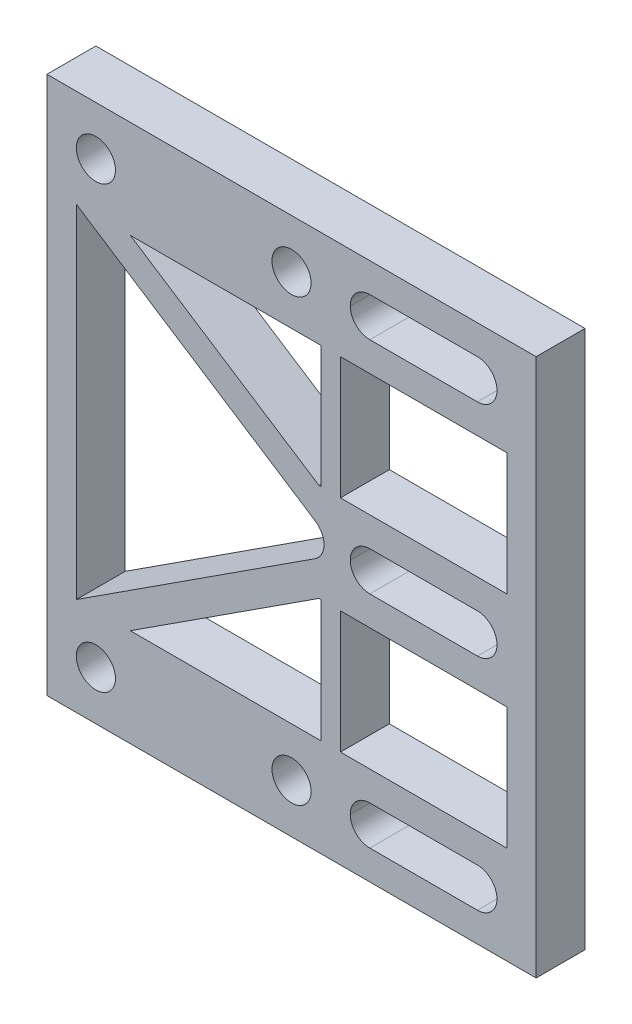
SolidWorks part; units mm, degrees
ref_plane "Front Plane" through (0, 0, 0) normal (0, 0, 1) x (1, 0, 0)
ref_plane "Top Plane" through (0, 0, 0) normal (0, 1, 0) x (1, 0, 0)
ref_plane "Right Plane" through (0, 0, 0) normal (1, 0, 0) x (0, 0, -1)
sketch "Sketch1" plane through (0, 0, 0) normal (0, 0, 1) x (1, 0, 0)
  line L1 (-27.8588, 40.7425) -> (35.6412, 40.7425)
  line L2 (-27.8588, 40.7425) -> (-27.8588, -29.1075)
  line L3 (-27.8588, -29.1075) -> (35.6412, -29.1075)
  line L4 (35.6412, 40.7425) -> (35.6412, -29.1075)
  dimension "D1" = 63.5
  dimension "D2" = 69.85
extrude "Boss-Extrude1" add sketch "Sketch1" along normal blind 6.35
sketch "Sketch2" plane through (0, 0, 6.35) normal (0, 0, 1) x (1, 0, 0)
  line L0 (35.6412, 40.7425) -> (-27.8588, 40.7425) construction
  line L2 (11.5112, 36.9325) -> (30.5612, 36.9325)
  line L3 (11.5112, 36.9325) -> (11.5112, 31.8525)
  line L4 (11.5112, 31.8525) -> (30.5612, 31.8525)
  line L5 (30.5612, 36.9325) -> (30.5612, 31.8525)
  line L6 (11.5112, -20.2175) -> (30.5612, -20.2175)
  line L7 (11.5112, -20.2175) -> (11.5112, -25.2975)
  line L8 (11.5112, -25.2975) -> (30.5612, -25.2975)
  line L9 (30.5612, -20.2175) -> (30.5612, -25.2975)
  line L10 (11.5112, 8.3575) -> (30.5612, 8.3575)
  line L11 (11.5112, 8.3575) -> (11.5112, 3.2775)
  line L12 (11.5112, 3.2775) -> (30.5612, 3.2775)
  line L13 (30.5612, 8.3575) -> (30.5612, 3.2775)
  line L14 (-27.8588, -29.1075) -> (35.6412, -29.1075) construction
  line L15 (35.6412, -29.1075) -> (35.6412, 40.7425) construction
  line L28 (-27.8588, 40.7425) -> (-27.8588, -29.1075) construction
  circle A0 centre (-21.5088, 34.3925) radius 2.54
  circle A1 centre (3.8912, 34.3925) radius 2.54
  circle A2 centre (-21.5088, -22.7575) radius 2.54
  circle A3 centre (3.8912, -22.7575) radius 2.54
  dimension "D1" = 5.08
  dimension "D2" = 6.35
  dimension "D3" = 57.15
  dimension "D4" = 5.08
  dimension "D5" = 5.08
  dimension "D6" = 3.81
  dimension "D7" = 3.81
  dimension "D8" = 32.385
  dimension "D9" = 19.05
  dimension "D10" = 6.35
  dimension "D12" = 25.4
extrude "Cut-Extrude1" cut sketch "Sketch2" against normal blind 6.35
fillet "Fillet1" radius 2.54 12 edges at (30.5612, 31.8525, 3.175) (30.5612, 3.2775, 3.175) (30.5612, -25.2975, 3.175) (30.5612, -20.2175, 3.175) (30.5612, 8.3575, 3.175) (30.5612, 36.9325, 3.175) (11.5112, -20.2175, 3.175) (11.5112, 8.3575, 3.175) (11.5112, 36.9325, 3.175) (11.5112, 31.8525, 3.175) (11.5112, 3.2775, 3.175) (11.5112, -25.2975, 3.175)
sketch "Sketch3" plane through (0, 0, 6.35) normal (0, 0, 1) x (1, 0, 0)
  line L17 (-17.0438, -16.4075) -> (7.7012, -16.4075)
  line L18 (31.8312, -16.4075) -> (31.8312, -0.5325)
  line L19 (31.8312, -0.5325) -> (10.2412, -0.5325)
  line L20 (7.4491, -0.5325) -> (-17.0438, -16.4075)
  line L22 (-24.0488, -16.4075) -> (10.2412, 5.8175)
  line L23 (10.2412, 5.8175) -> (-24.0488, 28.0425)
  line L24 (-24.0488, 28.0425) -> (-24.0488, -16.4075)
  line L25 (-17.0438, 28.0425) -> (7.4491, 12.1675)
  line L26 (7.4491, 12.1675) -> (7.7012, 12.1675)
  line L27 (31.8312, 12.1675) -> (31.8312, 28.0425)
  line L28 (31.8312, 28.0425) -> (10.2412, 28.0425)
  line L29 (-27.8588, -29.1075) -> (35.6412, -29.1075) construction
  line L30 (35.6412, -29.1075) -> (35.6412, 40.7425) construction
  line L31 (-27.8588, 40.7425) -> (-27.8588, -29.1075) construction
  line L32 (7.7012, 12.1675) -> (7.7012, 28.0425)
  line L33 (7.7012, -0.5325) -> (7.7012, -16.4075)
  line L34 (10.2412, 12.1675) -> (10.2412, 28.0425)
  line L35 (10.2412, -0.5325) -> (10.2412, -16.4075)
  line L36 (7.7012, 28.0425) -> (-17.0438, 28.0425)
  line L37 (10.2412, 12.1675) -> (31.8312, 12.1675)
  line L38 (10.2412, -16.4075) -> (31.8312, -16.4075)
  line L39 (7.7012, -0.5325) -> (7.4491, -0.5325)
  dimension "D1" = 34.925
  dimension "D2" = 3.81
  dimension "D3" = 25.4
  dimension "D4" = 3.81
  dimension "D5" = 3.81
  dimension "D6" = 44.45
  dimension "D7" = 3.81
  dimension "D8" = 15.875
  dimension "D9" = 2.54
extrude "Cut-Extrude2" cut sketch "Sketch3" against normal blind 7.62
fillet "Fillet3" radius 2.54 1 edges at (10.2412, 5.8175, 3.175)
